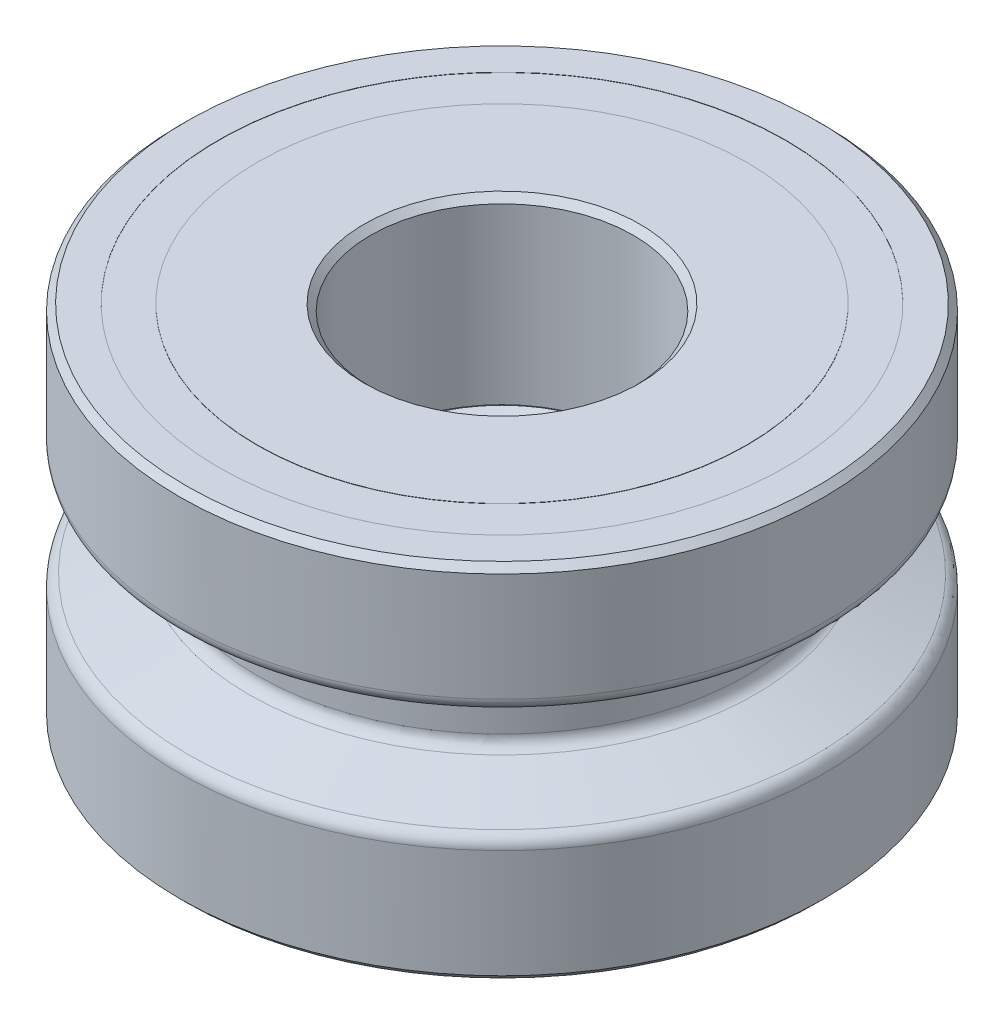
SolidWorks part; units mm, degrees
ref_plane "Front Plane" through (0, 0, 0) normal (0, 0, 1) x (1, 0, 0)
ref_plane "Top Plane" through (0, 0, 0) normal (0, 1, 0) x (1, 0, 0)
ref_plane "Right Plane" through (0, 0, 0) normal (1, 0, 0) x (0, 0, -1)
sketch "Sketch1" plane through (0, 0, 0) normal (0, 1, 0) x (1, 0, 0)
  circle A0 centre (0, 0) radius 12.5
  dimension "D1" = 25
extrude "Boss-Extrude1" add sketch "Sketch1" along normal mid plane 14
sketch "Sketch2" plane through (0, -7, 0) normal (0, -1, 0) x (1, 0, 0)
  circle A1 centre (0, 0) radius 4
  dimension "D1" = 8
extrude "Cut-Extrude1" cut sketch "Sketch2" against normal up to next
sketch "Sketch11" plane through (0, -7, 0) normal (0, -1, 0) x (1, 0, 0)
  circle A0 centre (0, 0) radius 5.1
  dimension "D1" = 10.2
extrude "Cut-Extrude5" cut sketch "Sketch11" against normal blind 4
sketch "Sketch12" plane through (0, 7, 0) normal (0, 1, 0) x (1, 0, 0)
  circle A0 centre (0, 0) radius 5.1 construction
  circle A1 centre (0, 0) radius 5.1
extrude "Cut-Extrude6" cut sketch "Sketch12" against normal blind 7
sketch "Sketch7" plane through (0, 7, 0) normal (0, 1, 0) x (1, 0, 0)
  circle A1 centre (0, 0) radius 9.5
  circle A2 centre (0, 0) radius 11
  circle A3 centre (0, 0) radius 11
  dimension "D1" = 1.5
  dimension "D2" = 1.5
extrude "Cut-Extrude4" cut sketch "Sketch7" against normal blind 0.01 contours A3 A1 region at (-10.6889, 7, 0)
ref_axis "Axis1" through (0, 7, 0) along (0, -1, 0)
sketch "Sketch10" plane through (0, 0, 0) normal (0, 0, 1) x (1, 0, 0)
  line L0 (-4.2808, 0) -> (5.2603, 0) construction
  line L1 (12.5, 2.1919) -> (9.5, 1.1)
  line L2 (12.5, -7) -> (12.5, 7) construction
  line L4 (12.5, -2.1919) -> (9.5, -1.1)
  line L5 (12.5, 2.1919) -> (12.5, -2.1919)
  line L6 (9.5, 1.1) -> (9.5, -1.1)
  line L7 (9.5, 1.1) -> (12.5, 1.1) construction
  dimension "D1" = 3
  dimension "D2" = 2.2
  dimension "D3" = 20
revolve "Cut-Revolve1" cut sketch "Sketch10" angle 360 about axis through (0, 7, 0) along (0, -1, 0)
chamfer "Chamfer2" distance 0.5 angle 65 1 edges at (0, 0, 4) first distance on face at (0, -3, -4)
fillet "Fillet4" radius 0.5 4 edges at (0, -1.1, 9.5) (0, 1.1, 9.5) (0, 2.1919, 12.5) (0, -2.1919, 12.5)
chamfer "Chamfer1" distance 0.25 angle 45 5 edges at (0, -7, 12.5) (0, 7, 12.5) (0, -7, -5.1) (0, 7, 5.1) (0, -3, -4)
